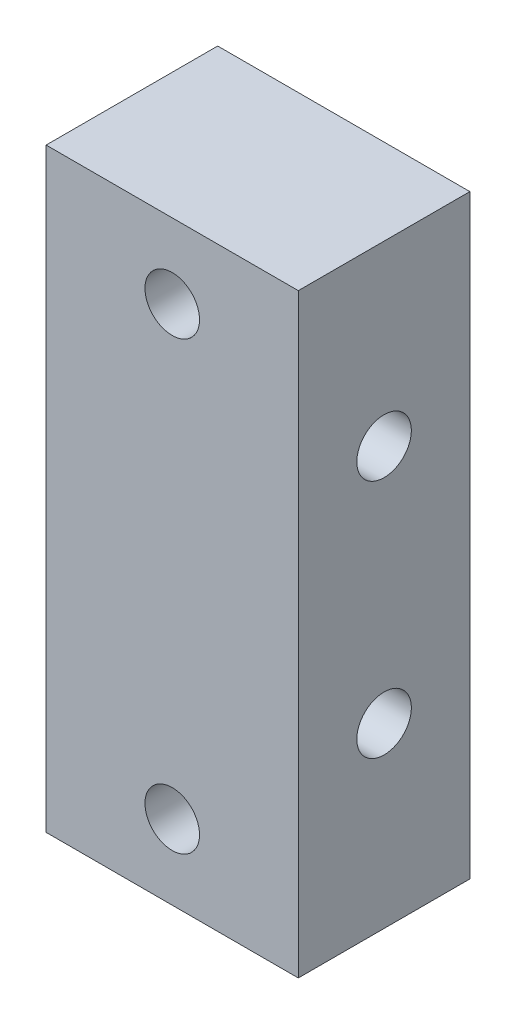
SolidWorks part; units mm, degrees
ref_plane "Front Plane" through (0, 0, 0) normal (0, 0, 1) x (1, 0, 0)
ref_plane "Top Plane" through (0, 0, 0) normal (0, 1, 0) x (1, 0, 0)
ref_plane "Right Plane" through (0, 0, 0) normal (1, 0, 0) x (0, 0, -1)
sketch "Sketch1" plane through (0, 0, 0) normal (0, 0, 1) x (1, 0, 0)
  line L1 (-9.3345, 22.0345) -> (9.3345, 22.0345)
  line L2 (-9.3345, 22.0345) -> (-9.3345, -22.0345)
  line L3 (-9.3345, -22.0345) -> (9.3345, -22.0345)
  line L4 (9.3345, 22.0345) -> (9.3345, -22.0345)
  line L5 (-9.3345, 22.0345) -> (9.3345, -22.0345) construction
  line L6 (-9.3345, -22.0345) -> (9.3345, 22.0345) construction
  point P0 (0, 0)
  dimension "D1" = 18.669
  dimension "D2" = 44.069
extrude "Boss-Extrude1" add sketch "Sketch1" along normal blind 12.7
sketch "Sketch2" plane through (9.3345, 0, 0) normal (1, 0, 0) x (0, 0, -1)
  line L0 (-6.35, 8.89) -> (-6.35, -8.89) construction
  line L1 (-12.7, -22.0345) -> (-12.7, 22.0345) construction
  line L2 (0, -22.0345) -> (0, 22.0345) construction
  point P2 (-6.35, 0)
  point P7 (0, 0)
  dimension "D1" = 6.35
  dimension "D2" = 17.78
hole_wizard "Tap Drill for #10-32 Tap1" positions "Sketch3" profile "Sketch4" hole size "#10-32" standard "ANSI Inch" end condition through all
sketch "Sketch3" plane through (9.3345, 0, 0) normal (1, 0, 0) x (0, 0, -1)
  point P0 (-6.35, 8.89)
  point P3 (-6.35, -8.89)
sketch "Sketch4" plane through (9.3345, 8.89, 6.35) normal (0, 1, 0) x (0, 0, -1)
  line L0 (0, 0) -> (0, 18.669)
  line L1 (0, 18.669) -> (2.0193, 18.669)
  line L2 (2.0193, 18.669) -> (2.0193, 0)
  line L5 (2.0193, 0) -> (0, 0)
  line L11 (0, -6.35) -> (0, 107.95) construction
  dimension "Thru Hole Dia." = 4.0386
  dimension "Thru Hole Depth" = 18.669
sketch "Sketch5" plane through (0, 0, 12.7) normal (0, 0, 1) x (1, 0, 0)
  line L0 (0, 16.51) -> (0, -16.51) construction
  point P3 (0, 0)
  dimension "D1" = 33.02
hole_wizard "Tap Drill for #10-32 Tap2" positions "Sketch6" profile "Sketch8" hole size "#10-32" standard "ANSI Inch"
sketch "Sketch6" plane through (0, 0, 12.7) normal (0, 0, 1) x (1, 0, 0)
  point P0 (0, 16.51)
  point P3 (0, -16.51)
sketch "Sketch8" plane through (0, 16.51, 12.7) normal (1, 0, 0) x (0, -1, 0)
  line L0 (0, 0) -> (0, 7.5633)
  line L1 (0, 7.5633) -> (2.0193, 6.35)
  line L2 (2.0193, 6.35) -> (2.0193, 0)
  line L5 (2.0193, 0) -> (0, 0)
  line L10 (0, 7.5633) -> (-2.0193, 6.35) construction
  line L11 (0, -6.35) -> (0, 107.95) construction
  dimension "Hole Dia." = 4.0386
  dimension "Hole Depth" = 6.35
  dimension "Drill Angle" = 118
